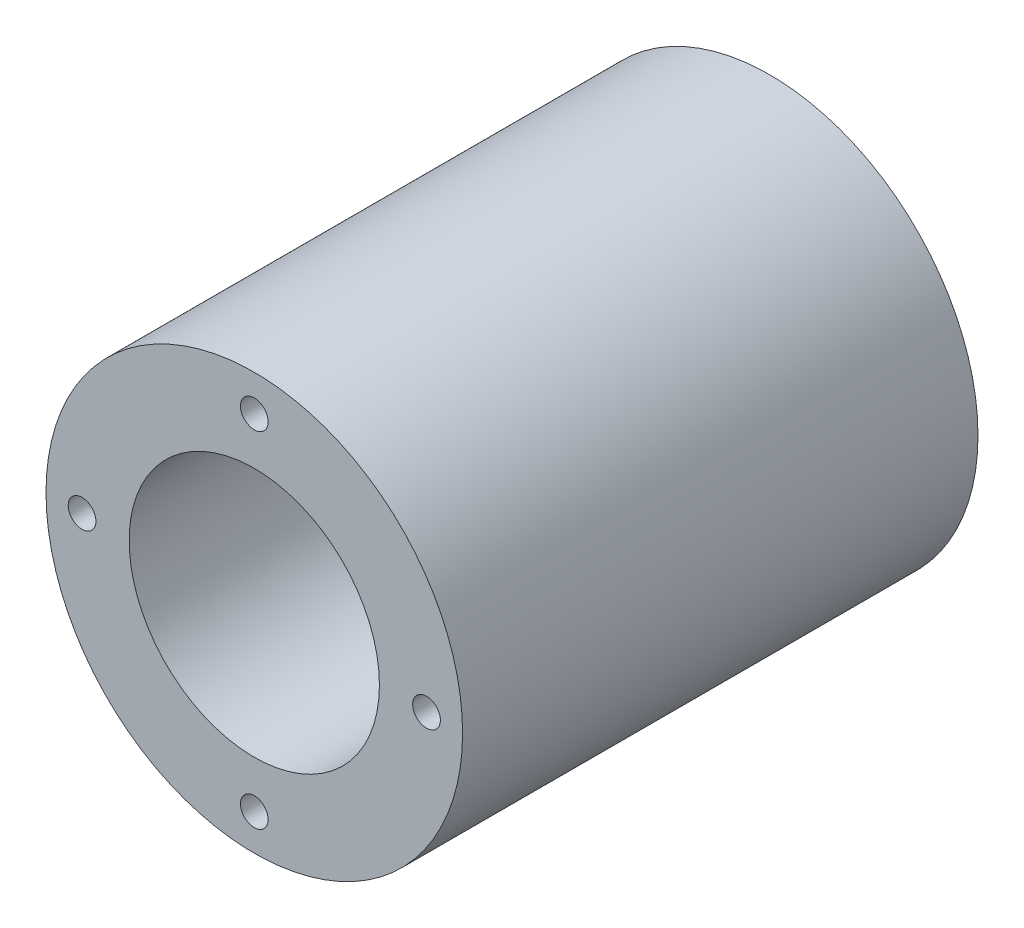
SolidWorks part; units mm, degrees
material "6061-T6 (SS)"
ref_plane "Front Plane" through (0, 0, 0) normal (0, 0, 1) x (1, 0, 0)
ref_plane "Top Plane" through (0, 0, 0) normal (0, 1, 0) x (1, 0, 0)
ref_plane "Right Plane" through (0, 0, 0) normal (1, 0, 0) x (0, 0, -1)
sketch "Sketch Spindle Skeleton" plane through (0, 0, 0) normal (1, 0, 0) x (0, 0, -1)
  line L0 (-95.847, -9.5) -> (-144, -9.5)
  line L5 (-1000, 0) -> (49000, 0)
  line L6 (0, -9.5) -> (0, 9.5)
  line L13 (0, 9.5) -> (-45.847, 9.5)
  line L26 (-45.847, 9.5) -> (-45.847, 14)
  line L27 (-45.847, 14) -> (-95.847, 14)
  line L32 (-95.847, 14) -> (-95.847, 9.5)
  line L34 (-160, 7) -> (-160, -7)
  line L36 (-95.847, -9.5) -> (-95.847, -14)
  line L37 (-95.847, -14) -> (-45.847, -14)
  line L38 (-45.847, -14) -> (-45.847, -9.5)
  line L39 (0, -9.5) -> (-45.847, -9.5)
  line L40 (-25.305, 37.6491) -> (-16.305, 37.6491)
  line L41 (-111.341, 22.6187) -> (-95.847, 22.6187)
  line L42 (-111.341, 22.6187) -> (-111.341, -22.6187)
  line L43 (-111.341, -22.6187) -> (-95.847, -22.6187)
  line L44 (-95.847, 22.6187) -> (-95.847, -22.6187)
  line L45 (-111.341, 22.6187) -> (-95.847, -22.6187) construction
  line L46 (-111.341, -22.6187) -> (-95.847, 22.6187) construction
  line L47 (-30.353, 22.6187) -> (-45.847, 22.6187)
  line L48 (-30.353, 22.6187) -> (-30.353, -22.6187)
  line L49 (-30.353, -22.6187) -> (-45.847, -22.6187)
  line L50 (-45.847, 22.6187) -> (-45.847, -22.6187)
  line L51 (-30.353, 22.6187) -> (-45.847, -22.6187) construction
  line L52 (-30.353, -22.6187) -> (-45.847, 22.6187) construction
  line L59 (-16.305, 37.6491) -> (-16.305, -37.6491)
  line L60 (-16.305, -37.6491) -> (-25.305, -37.6491)
  line L61 (-25.305, -22.6187) -> (-27.305, -22.6187)
  line L62 (-27.305, -22.6187) -> (-27.305, -12.5)
  line L63 (-27.305, -12.5) -> (-25.305, -12.5)
  line L64 (-25.305, -12.5) -> (-25.305, 12.5)
  line L65 (-25.305, 12.5) -> (-27.305, 12.5)
  line L66 (-27.305, 12.5) -> (-27.305, 22.6187)
  line L67 (-27.305, 22.6187) -> (-25.305, 22.6187)
  line L68 (-25.305, 22.6187) -> (-25.305, 37.6491)
  line L69 (-25.305, -22.6187) -> (-25.305, -37.6491)
  line L71 (-119.469, 37.6491) -> (-26.305, 37.6491)
  line L72 (-119.469, 37.6491) -> (-119.469, -37.6491)
  line L73 (-119.469, -37.6491) -> (-26.305, -37.6491)
  line L74 (-26.305, 37.6491) -> (-26.305, -37.6491)
  line L75 (-119.469, 37.6491) -> (-26.305, -37.6491) construction
  line L76 (-119.469, -37.6491) -> (-26.305, 37.6491) construction
  line L77 (-144, -9.5) -> (-144, -7)
  line L78 (-144, -7) -> (-160, -7)
  line L79 (-95.847, 9.5) -> (-144, 9.5)
  line L80 (-144, 7) -> (-160, 7)
  line L81 (-144, 9.5) -> (-144, 7)
  line L82 (-119.9235, 9.5) -> (-119.9235, -9.5) construction
  line L83 (-22.9235, 9.5) -> (-22.9235, -9.5) construction
  line L96 (-119.469, 37.6491) -> (-128.469, 37.6492)
  line L98 (-119.469, -37.6491) -> (-128.469, -37.6491)
  line L99 (-128.469, 37.6492) -> (-128.469, -37.6491)
  line L110 (-119.469, 37.6491) -> (-119.469, -37.6491)
  point P3 (0, 0)
  point P18 (-103.594, 0)
  point P24 (-38.1, 0)
  point P29 (-72.887, 0)
  point P48 (-16.305, 31.1339)
  point P70 (-128.469, 31.1339)
sketch "Sketch1" plane through (0, 0, 0) normal (1, 0, 0) x (0, 0, -1)
  line L0 (-26.305, 37.6491) -> (-26.305, -37.6491) construction
  line L1 (-119.469, -37.6491) -> (-26.305, -37.6491) construction
  line L2 (-119.469, 37.6491) -> (-119.469, -37.6491) construction
  line L3 (-119.469, 37.6491) -> (-26.305, 37.6491) construction
  line L4 (-26.305, 37.6491) -> (-26.305, -37.6491)
  line L5 (-119.469, -37.6491) -> (-26.305, -37.6491)
  line L6 (-119.469, 37.6491) -> (-119.469, -37.6491)
  line L7 (-119.469, 37.6491) -> (-26.305, 37.6491)
  line L9 (-30.353, 22.6187) -> (-45.847, 22.6187) construction
  line L10 (-119.469, 22.6187) -> (-26.305, 22.6187)
  line L15 (-119.469, 0) -> (-26.305, 0) construction
revolve "Revolve1" add sketch "Sketch1" angle 360 about L15 region at (0, 30.1339, 72.887)
sketch "Back Hole Top Location" plane through (0, 0, 26.305) normal (0, 0, -1) x (-1, 0, 0)
  point P9 (0, 31.1339)
hole_wizard "M6x1.0 Tapped Hole3" positions "Sketch8" profile "Sketch9" tap size "M6x1.0" standard "ANSI Metric"
sketch "Sketch8" plane through (0, 0, 26.305) normal (0, 0, -1) x (-1, 0, 0)
  point P0 (0, 31.1339)
sketch "Sketch9" plane through (0, 31.1339, 26.305) normal (1, 0, 0) x (0, 1, 0)
  line L0 (0, 0) -> (0, 16.5022)
  line L1 (0, 16.5022) -> (2.5, 15)
  line L2 (2.5, 15) -> (2.5, 0)
  line L5 (2.5, 0) -> (0, 0)
  line L10 (0, 16.5022) -> (-2.5, 15) construction
  line L11 (0, -6.35) -> (0, 107.95) construction
  dimension "Tap Drill Dia." = 5
  dimension "Tap Drill Depth" = 15
  dimension "Drill Angle" = 118
pattern_circular "BackFacePattern" count 6 over 360 about axis through (0, 0, 1000) along (0, 0, -1) of "M6x1.0 Tapped Hole3"
ref_plane "Midplane" through (0, 0, 72.887) normal (0, 0, -1) x (-1, 0, 0)
sketch "Front Hole Top Location" plane through (0, 0, 119.469) normal (0, 0, 1) x (1, 0, 0)
  point P0 (0, 31.1339)
hole_wizard "M6x1.0 Tapped Hole2" positions "Sketch5" profile "Sketch6" tap size "M6x1.0" standard "ANSI Metric"
sketch "Sketch5" plane through (0, 0, 119.469) normal (0, 0, 1) x (1, 0, 0)
  point P0 (0, 31.1339)
sketch "Sketch6" plane through (0, 31.1339, 119.469) normal (1, 0, 0) x (0, -1, 0)
  line L0 (0, 0) -> (0, 16.5022)
  line L1 (0, 16.5022) -> (2.5, 15)
  line L2 (2.5, 15) -> (2.5, 0)
  line L5 (2.5, 0) -> (0, 0)
  line L10 (0, 16.5022) -> (-2.5, 15) construction
  line L11 (0, -6.35) -> (0, 107.95) construction
  dimension "Tap Drill Dia." = 5
  dimension "Tap Drill Depth" = 15
  dimension "Drill Angle" = 118
pattern_circular "FrontFacePattern" count 4 over 360 about axis through (0, 0, 1000) along (0, 0, -1) of "M6x1.0 Tapped Hole2"
sketch "Sketch7" plane through (0, 0, 26.305) normal (0, 0, -1) x (-1, 0, 0)
  circle A0 centre (0, 0) radius 26.9875
  circle A1 centre (0, 0) radius 24.6062
  dimension "D1" = 53.975
  dimension "D2" = 49.2125
extrude "Cut-Extrude1" cut sketch "Sketch7" against normal blind 0.5
